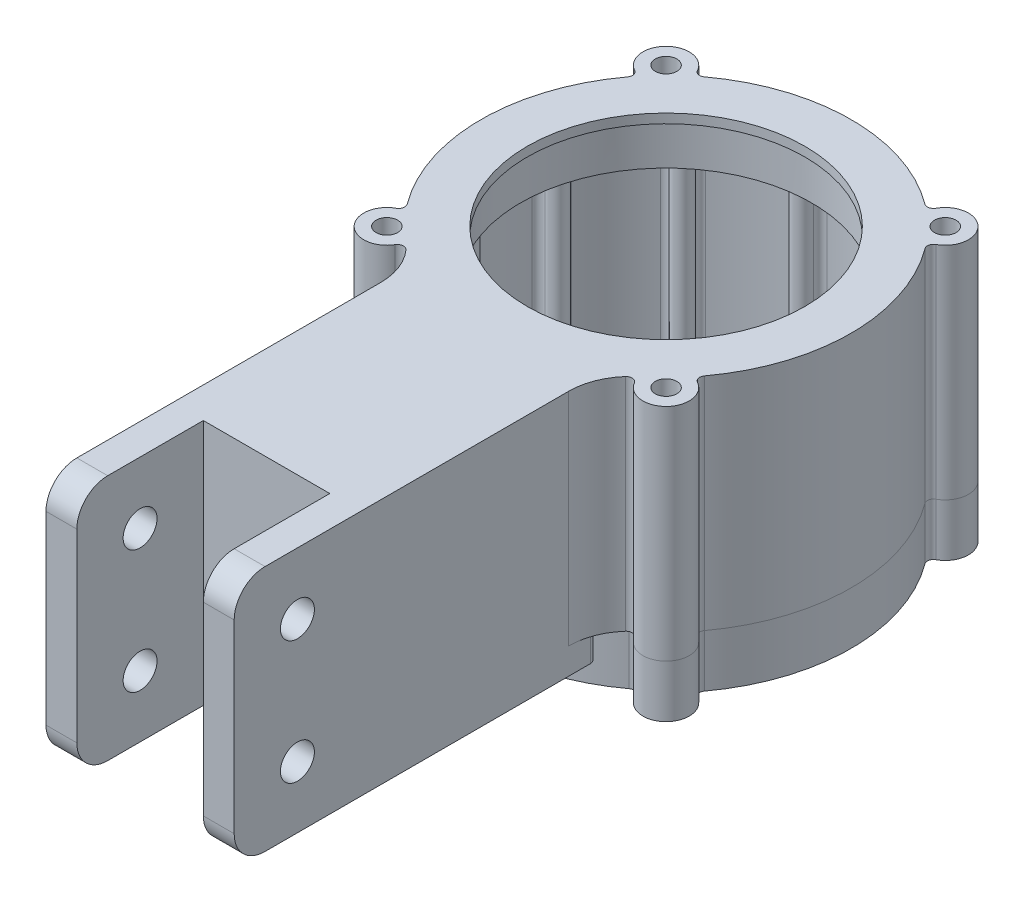
SolidWorks part; units mm, degrees
material "ABS"
ref_plane "Front Plane" through (0, 0, 0) normal (0, 0, 1) x (1, 0, 0)
ref_plane "Top Plane" through (0, 0, 0) normal (0, 1, 0) x (1, 0, 0)
ref_plane "Right Plane" through (0, 0, 0) normal (1, 0, 0) x (0, 0, -1)
ref_axis "Housing Axis" through (0, -42.2781, 0) along (0, -1, 0)
sketch "Sketch1" plane through (0, 0, 0) normal (0, 1, 0) x (1, 0, 0)
  line L0 (0, 0) -> (26.3502, 7.7371) construction
  line L1 (0, 0) -> (26.3502, -7.7371) construction
  line L2 (0, 0) -> (26, 0) construction
  line L3 (26.3502, 7.7371) -> (28.7848, 8.452)
  line L4 (26.3502, -7.7371) -> (28.7848, -8.452)
  circle A0 centre (0, 0) radius 26 construction
  arc A1 (26.2079, 1.4855) -> (26.2079, -1.4855) centre (26, 0) ccw
  arc A2 (26.3502, 7.7371) -> (27.3422, 2.5694) centre (0, 0) cw
  arc A3 (27.3422, -2.5694) -> (26.3502, -7.7371) centre (0, 0) cw
  arc A4 (26.2079, 1.4855) -> (27.3422, 2.5694) centre (26.3466, 2.4759) ccw
  arc A5 (26.2079, -1.4855) -> (27.3422, -2.5694) centre (26.3466, -2.4759) cw
  arc A6 (26.2079, 1.4855) -> (26.2079, -1.4855) centre (0, 0) cw construction
  arc A7 (28.7848, 8.452) -> (28.7848, -8.452) centre (0, 0) cw
  point P14 (27.4605, -0.342)
  dimension "D1" = 52
  dimension "D2" = 3
  dimension "D5" = 1
  dimension "D6" = 30
  dimension "D3" = 32.727
  dimension "D4" = 0.25
extrude "Boss-Extrude1" add sketch "Sketch1" along normal mid plane 27.25
sketch "Sketch2" plane through (0, 13.625, 0) normal (0, 1, 0) x (1, 0, 0)
  circle A0 centre (0, 0) radius 30
  circle A1 centre (0, 0) radius 22.5
  circle A2 centre (0, 0) radius 30 construction
  dimension "D1" = 45
extrude "Boss-Extrude2" add sketch "Sketch2" along normal blind 8.5
pattern_circular "CirPattern1" count 11 over 360 about axis through (0, -42.2781, 0) along (0, -1, 0) of "Boss-Extrude1"
sketch "Sketch3" plane through (0, 22.125, 0) normal (0, -1, 0) x (-1, 0, 0)
  circle A0 centre (0, 0) radius 23.6
  dimension "D1" = 47.2
extrude "Cut-Extrude1" cut sketch "Sketch3" along normal through all from offset 1.5
sketch "Sketch4" plane through (0, 22.125, 0) normal (0, 1, 0) x (1, 0, 0)
  line L0 (-10.25, -85.25) -> (-10.25, -64.75)
  line L1 (-10.25, -64.75) -> (10.25, -64.75)
  line L2 (10.25, -64.75) -> (10.25, -85.25)
  line L3 (10.25, -85.25) -> (-10.25, -64.75) construction
  line L4 (0, -75) -> (0, 0) construction
  line L5 (10.25, -85.25) -> (15.25, -85.25)
  line L6 (15.25, -85.25) -> (15.25, -25.8348)
  line L7 (-10.25, -85.25) -> (-15.25, -85.25)
  line L8 (-15.25, -85.25) -> (-15.25, -25.8348)
  circle A0 centre (0, 0) radius 30 construction
  arc A1 (15.25, -25.8348) -> (-15.25, -25.8348) centre (0, 0) cw
  dimension "D3" = 5
  dimension "D1" = 20.5
  dimension "D2" = 75
extrude "Boss-Extrude3" add sketch "Sketch4" against normal blind 40
fillet "Fillet1" radius 10 2 edges at (15.25, 4.25, 25.8348) (-15.25, 4.25, 25.8348)
fillet "Fillet2" radius 1 2 edges at (-15.25, -15.75, 25.8348) (15.25, -15.75, 25.8348)
sketch "Sketch5" plane through (15.25, 0, 0) normal (1, 0, 0) x (0, 0, -1)
  line L0 (-75, 22.125) -> (-75, 12.125) construction
  line L1 (-85.25, 22.125) -> (-31.0232, 22.125) construction
  line L2 (-75, 12.125) -> (-75, -7.875) construction
  line L3 (-75, -7.875) -> (-75, -17.875) construction
  line L4 (-85.25, -17.875) -> (-27.5307, -17.875) construction
  line L5 (-85.25, 22.125) -> (-64.75, 22.125) construction
  circle A0 centre (-75, 12.125) radius 2.75
  circle A1 centre (-75, -7.875) radius 2.75
  dimension "D2" = 5.5
  dimension "D1" = 20
extrude "Cut-Extrude2" cut sketch "Sketch5" against normal through all both
fillet "Fillet3" radius 5 4 edges at (12.75, -17.875, 85.25) (-12.75, -17.875, 85.25) (12.75, 22.125, 85.25) (-12.75, 22.125, 85.25)
sketch "Sketch6" plane through (0, -13.625, 0) normal (0, -1, 0) x (1, 0, 0)
  line L0 (0, 0) -> (22.6274, 22.6274) construction
  line L1 (0, 0) -> (22.6274, -22.6274) construction
  line L2 (0, 0) -> (-22.6274, -22.6274) construction
  line L3 (0, 0) -> (-22.6274, 22.6274) construction
  line L4 (-22.6274, 22.6274) -> (22.6274, 22.6274) construction
  line L5 (22.6274, 22.6274) -> (22.6274, -22.6274) construction
  line L6 (-15.25, 31.0232) -> (15.25, 31.0232)
  circle A0 centre (22.6274, 22.6274) radius 1.75
  circle A1 centre (22.6274, -22.6274) radius 1.75
  circle A2 centre (-22.6274, -22.6274) radius 1.75
  circle A3 centre (-22.6274, 22.6274) radius 1.75
  arc A4 (24.4256, 19.3366) -> (19.3943, 24.5273) centre (22.6274, 22.6274) ccw
  arc A5 (19.3366, -24.4256) -> (24.4256, -19.3366) centre (22.6274, -22.6274) ccw
  arc A6 (-24.4256, -19.3366) -> (-19.3366, -24.4256) centre (-22.6274, -22.6274) ccw
  arc A7 (-19.3943, 24.5273) -> (-24.4256, 19.3366) centre (-22.6274, 22.6274) ccw
  arc A8 (-18.9375, 23.2674) -> (-15.25, 31.0232) centre (-25.25, 31.0232) ccw construction
  arc A9 (24.1017, 17.8636) -> (24.4256, 19.3366) centre (24.9051, 18.4591) cw
  arc A10 (15.25, 31.0232) -> (18.9375, 23.2674) centre (25.25, 31.0232) ccw construction
  arc A11 (-18.9375, 23.2674) -> (-18.9331, 23.271) centre (-25.25, 31.0232) ccw
  arc A12 (-17.8636, -24.1017) -> (17.8636, -24.1017) centre (0, 0) ccw
  arc A13 (15.25, 31.0232) -> (17.7857, 24.3685) centre (25.25, 31.0232) ccw
  arc A14 (-24.1017, 17.8636) -> (-24.1017, -17.8636) centre (0, 0) ccw
  arc A15 (24.1017, -17.8636) -> (24.1017, 17.8636) centre (0, 0) ccw
  arc A16 (-18.9375, 23.2674) -> (18.9375, 23.2674) centre (0, 0) ccw construction
  arc A17 (24.4256, -19.3366) -> (24.1017, -17.8636) centre (24.9051, -18.4591) cw
  arc A18 (17.8636, -24.1017) -> (19.3366, -24.4256) centre (18.4591, -24.9051) cw
  arc A19 (-19.3366, -24.4256) -> (-17.8636, -24.1017) centre (-18.4591, -24.9051) cw
  arc A20 (-24.4256, -19.3366) -> (-24.1017, -17.8636) centre (-24.9051, -18.4591) ccw
  arc A21 (-24.4256, 19.3366) -> (-24.1017, 17.8636) centre (-24.9051, 18.4591) cw
  arc A22 (-19.3943, 24.5273) -> (-17.7857, 24.3685) centre (-18.5322, 25.034) ccw
  arc A23 (17.7857, 24.3685) -> (19.3943, 24.5273) centre (18.5322, 25.034) ccw
  arc A24 (-17.7857, 24.3685) -> (-15.25, 31.0232) centre (-25.25, 31.0232) ccw
  circle A25 centre (0, 0) radius 27.4626
  arc A26 (9.0211, 25.9387) -> (-1.3479, 27.4295) centre (0, 0) ccw construction
  point P13 (0, 0)
  point P36 (-18.9331, -23.271)
  dimension "D1" = 4
  dimension "D3" = 3.5
  dimension "D4" = 7.5
  dimension "D5" = 1
  dimension "D2" = 32
extrude "Boss-Extrude4" add sketch "Sketch6" against normal up to surface (35.75 mm away) contours A24 A22 A7 A21 A14 A20 A6 A19 A12 A18 A5 A17 A15 A9 A4 A23 A13 L6 A25 A3 A2 A1 A0 region at (0, -13.625, 30.1674) up to face at (0, 22.125, 50.4982)
sketch "Sketch7" plane through (0, -13.625, 0) normal (0, -1, 0) x (1, 0, 0)
  arc A0 (-19.163, 24.0628) -> (-24.4256, 19.3366) centre (-22.6274, 22.6274) ccw
  arc A1 (-24.4256, -19.3366) -> (-19.3366, -24.4256) centre (-22.6274, -22.6274) ccw
  arc A2 (24.4256, 19.3366) -> (19.163, 24.0628) centre (22.6274, 22.6274) ccw
  arc A3 (19.3366, -24.4256) -> (24.4256, -19.3366) centre (22.6274, -22.6274) ccw
  circle A4 centre (-22.6274, 22.6274) radius 1.75 construction
  circle A5 centre (-22.6274, -22.6274) radius 1.75 construction
  circle A6 centre (22.6274, -22.6274) radius 1.75 construction
  circle A7 centre (22.6274, 22.6274) radius 1.75 construction
  circle A8 centre (-22.6274, 22.6274) radius 1.75
  circle A9 centre (-22.6274, -22.6274) radius 1.75
  circle A10 centre (22.6274, -22.6274) radius 1.75
  circle A11 centre (22.6274, 22.6274) radius 1.75
  arc A12 (-19.3943, 24.5273) -> (-24.4256, 19.3366) centre (-22.6274, 22.6274) ccw construction
  arc A13 (-24.4256, -19.3366) -> (-24.1017, -17.8636) centre (-24.9051, -18.4591) ccw construction
  arc A14 (-24.1017, 17.8636) -> (-24.1017, -17.8636) centre (0, 0) ccw construction
  arc A15 (-24.1017, 17.8636) -> (-24.4256, 19.3366) centre (-24.9051, 18.4591) ccw construction
  arc A16 (-24.4256, -19.3366) -> (-24.1017, -17.8636) centre (-24.9051, -18.4591) ccw
  arc A17 (-24.1017, 17.8636) -> (-24.1017, -17.8636) centre (0, 0) ccw
  arc A18 (-24.1017, 17.8636) -> (-24.4256, 19.3366) centre (-24.9051, 18.4591) ccw
  arc A22 (24.1017, -17.8636) -> (24.4256, -19.3366) centre (24.9051, -18.4591) ccw
  arc A23 (24.1017, -17.8636) -> (24.1017, 17.8636) centre (0, 0) ccw
  arc A24 (24.4256, 19.3366) -> (24.1017, 17.8636) centre (24.9051, 18.4591) ccw
  arc A25 (-17.8636, -24.1017) -> (-19.3366, -24.4256) centre (-18.4591, -24.9051) ccw
  arc A26 (-17.8636, -24.1017) -> (17.8636, -24.1017) centre (0, 0) ccw
  arc A27 (19.3366, -24.4256) -> (17.8636, -24.1017) centre (18.4591, -24.9051) ccw
  circle A28 centre (0, 0) radius 23.6
  circle A29 centre (0, 0) radius 23.6 construction
  arc A30 (17.8636, 24.1017) -> (-17.8636, 24.1017) centre (0, 0) ccw [skipped]
  arc A31 (17.8636, 24.1017) -> (19.3366, 24.4256) centre (18.4591, 24.9051) ccw [skipped]
  arc A32 (-19.3366, 24.4256) -> (-17.8636, 24.1017) centre (-18.4591, 24.9051) ccw [skipped]
  arc A33 (17.6411, 23.644) -> (-17.6411, 23.644) centre (0, 0) ccw
  arc A34 (13.7903, 26.6426) -> (-13.7903, 26.6426) centre (0, 0) ccw construction
  arc A35 (17.6411, 23.644) -> (19.163, 24.0628) centre (18.2391, 24.4455) ccw
  arc A36 (-17.6411, 23.644) -> (-19.163, 24.0628) centre (-18.2391, 24.4455) cw
  point P55 (0, 0)
  dimension "D1" = 4
  dimension "D2" = 0.5
extrude "Boss-Extrude5" add sketch "Sketch7" along normal blind 8.5 separate body
sketch "Sketch8" plane through (0, -22.125, 0) normal (0, -1, 0) x (1, 0, 0)
  circle A0 centre (0, 0) radius 22.5
  circle A1 centre (0, 0) radius 22.5 construction
  circle A2 centre (0, 0) radius 23.6 construction
  circle A3 centre (0, 0) radius 23.6
extrude "Boss-Extrude6" add sketch "Sketch8" against normal blind 1.5
sketch "Sketch9" plane through (0, -22.125, 0) normal (0, -1, 0) x (1, 0, 0)
  line L0 (0, 0) -> (-19.8823, 19.8823) construction
  line L1 (-27.291, 12.4736) -> (-12.4736, 27.291) construction
  line L2 (0, 0) -> (0, 29.5) construction
  circle A0 centre (-27.291, 12.4736) radius 2.35
  circle A1 centre (-12.4736, 27.291) radius 2.35
  arc A2 (17.6411, 23.644) -> (-17.6411, 23.644) centre (0, 0) ccw construction
  circle A3 centre (-12.4736, 27.291) radius 5
  circle A4 centre (-27.291, 12.4736) radius 5
  dimension "D1" = 20.955
  dimension "D2" = 4.7
  dimension "D5" = 10
  dimension "D3" = 28.1178
  dimension "D4" = 45
extrude "Boss-Extrude7" add sketch "Sketch9" along normal blind 2.856 and the other way blind 2
sketch "Sketch10" plane through (0, -24.981, 0) normal (0, -1, 0) x (1, 0, 0)
  circle A0 centre (-27.291, 12.4736) radius 2.35 construction
  circle A1 centre (-12.4736, 27.291) radius 2.35 construction
  circle A2 centre (-27.291, 12.4736) radius 2.35
  circle A3 centre (-12.4736, 27.291) radius 2.35
extrude "Cut-Extrude3" cut sketch "Sketch10" against normal blind 4
sketch "Sketch11" plane through (0, -20.125, 0) normal (0, 1, 0) x (1, 0, 0)
  circle A0 centre (-27.291, -12.4736) radius 5 construction
  circle A1 centre (-12.4736, -27.291) radius 5 construction
  circle A2 centre (-27.291, -12.4736) radius 5
  circle A3 centre (-12.4736, -27.291) radius 5
extrude "Boss-Extrude8" add sketch "Sketch11" against normal up to surface (0.856 mm away) up to face at (-26.2194, -20.981, 11.9838)
chamfer "Chamfer1" distance 6 angle 45 2 edges at (-27.2851, -20.125, 12.4709) (-12.263, -20.125, 26.8304)
sketch "Sketch12" plane through (0, -17.875, 0) normal (0, -1, 0) x (1, 0, 0)
  circle A0 centre (-12.4736, 27.291) radius 5.5
  circle A1 centre (-12.4736, 27.291) radius 5 construction
  dimension "D1" = 0.5
extrude "Cut-Extrude4" cut sketch "Sketch12" against normal up to vertex (3.75 mm away) up to point (-16.5617, -14.125, 24.4123)
sketch "Sketch13" plane through (0, -22.125, 0) normal (0, -1, 0) x (1, 0, 0)
  line L0 (-24.8256, 16.8431) -> (-30.3322, 20.579)
  line L1 (-30.3322, 20.579) -> (-20.2983, 29.9184)
  line L2 (-20.2983, 29.9184) -> (-16.5624, 24.4119)
  line L3 (-16.5624, 24.4119) -> (0, 0) construction
  line L4 (0, 0) -> (-24.8256, 16.8431) construction
  arc A0 (-22.7879, 18.8809) -> (-18.8942, 22.273) centre (-22.6274, 22.6274) ccw
  arc A1 (-22.7879, 18.8809) -> (-23.618, 18.4984) centre (-22.8307, 17.8818) ccw
  arc A2 (-24.1017, 17.8636) -> (-24.8352, 16.8289) centre (0, 0) ccw construction
  arc A3 (-18.5267, 22.9567) -> (-18.8942, 22.273) centre (-17.8987, 22.1785) ccw
  arc A4 (-16.5617, 24.4123) -> (-17.6411, 23.644) centre (0, 0) ccw construction
  arc A5 (-19.163, 24.0628) -> (-17.6411, 23.644) centre (-18.2391, 24.4455) ccw construction
  arc A6 (-24.8256, 16.8431) -> (-23.618, 18.4984) centre (0, 0) cw
  arc A8 (-16.5624, 24.4119) -> (-18.5267, 22.9567) centre (0, 0) ccw
  arc A10 (-16.5617, 24.4123) -> (-7.6216, 28.4985) centre (-12.4736, 27.291) ccw construction
  circle A11 centre (-27.291, 12.4736) radius 5 construction
  arc A12 (-19.163, 24.0628) -> (-24.4256, 19.3366) centre (-22.6274, 22.6274) ccw construction
  arc A13 (17.6411, 23.644) -> (-7.6216, 28.4985) centre (0, 0) ccw construction
  arc A14 (-28.9773, 7.7665) -> (-24.1017, -17.8636) centre (0, 0) ccw construction
extrude "Cut-Extrude5" cut sketch "Sketch13" against normal blind 3
equation "\"RotorRadius\"= 26mm"
equation "\"Eccentricity\"= 1.00mm"
equation "\"RollerRadius\"= 1.5mm"
equation "\"GearRatio\"= 10"
equation "\"RollerCount\"=\"GearRatio\" + 1"
equation "\"RotorThickness\"= 6mm"
equation "\"OutputRollerRadius\"= 1.5mm"
equation "\"OutputRollerCount\"= 6"
equation "\"OutputRollerHoleCircleRadius\"=\"RotorRadius\"- 4 * \"OutputRollerRadius\""
equation "\"RotorGap\"= 0.5mm"
equation "\"D1@Sketch1\"=\"RotorRadius\"*2"
equation "\"D2@Sketch1\"=2*\"RollerRadius\""
equation "\"rotorCount\"= 2"
equation "\"D1@Boss-Extrude1\"=(\"rotorCount\" + 2) * \"RotorThickness\" + 0.5mm * (\"rotorCount\" + 4.5)"
equation "\"D1@CirPattern1\"=\"GearRatio\" + 1"
equation "\"D3@Sketch1\"=360deg/(\"GearRatio\" + 1)"
